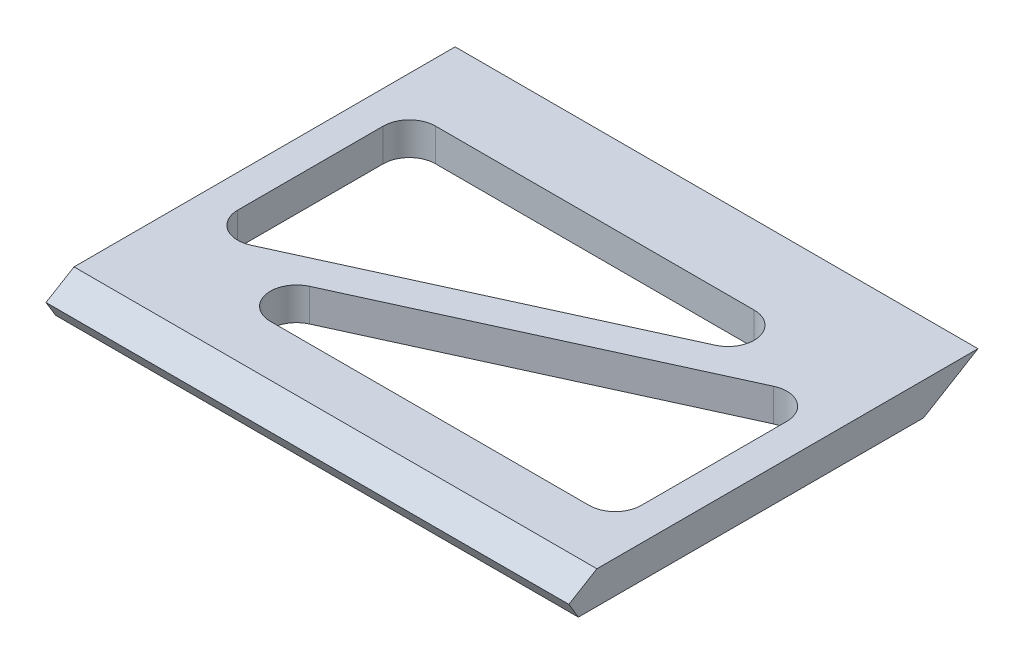
SolidWorks part; units mm, degrees
material "Balsa"
ref_plane "Front Plane" through (0, 0, 0) normal (0, 0, 1) x (1, 0, 0)
ref_plane "Top Plane" through (0, 0, 0) normal (0, 1, 0) x (1, 0, 0)
ref_plane "Right Plane" through (0, 0, 0) normal (1, 0, 0) x (0, 0, -1)
sketch "Sketch3" plane through (71.1933, 0, 0) normal (1, 0, 0) x (0, 0, -1)
  line L0 (56.968, 6.35) -> (46.3846, 0)
  line L1 (46.3846, 0) -> (-20.6804, 0)
  line L2 (-20.6804, 0) -> (-22.5302, 3.083)
  line L3 (-22.5302, 3.083) -> (-108.1269, 145.7441) construction
  line L4 (56.968, 6.35) -> (63.7199, 10.4011) construction
  line L6 (-22.5302, 3.083) -> (-17.0851, 6.35)
  line L7 (-17.0851, 6.35) -> (56.968, 6.35)
extrude "Boss-Extrude2" add sketch "Sketch3" against normal up to surface (101.6 mm away)
sketch "Sketch4" plane through (0, 6.35, 0) normal (0, 1, 0) x (1, 0, 0)
  line L0 (-30.4067, -17.0851) -> (-30.4067, 56.968) construction
  line L1 (-18.9767, 41.728) -> (42.949, 41.728)
  line L2 (-24.0567, 36.648) -> (-24.0567, 8.3732)
  line L3 (-2.1624, -7.1791) -> (59.7633, -7.1791)
  line L4 (64.8433, 26.1757) -> (64.8433, -2.0991)
  line L5 (-30.4067, 56.968) -> (71.1933, 56.968) construction
  line L6 (71.1933, 56.968) -> (71.1933, -17.0851) construction
  line L7 (-30.4067, -17.0851) -> (71.1933, -17.0851) construction
  line L8 (-16.8668, 3.7521) -> (45.0589, 32.0269)
  line L9 (-4.2724, 2.522) -> (57.6533, 30.7968)
  line L10 (-29.6117, -5.5575) -> (68.6464, 39.3064)
  arc A0 (-4.2724, 2.522) -> (-2.1624, -7.1791) centre (-2.1624, -2.0991) ccw
  arc A1 (59.7633, -7.1791) -> (64.8433, -2.0991) centre (59.7633, -2.0991) ccw
  arc A2 (57.6533, 30.7968) -> (64.8433, 26.1757) centre (59.7633, 26.1757) cw
  arc A3 (45.0589, 32.0269) -> (42.949, 41.728) centre (42.949, 36.648) ccw
  arc A4 (-18.9767, 41.728) -> (-24.0567, 36.648) centre (-18.9767, 36.648) ccw
  arc A5 (-16.8668, 3.7521) -> (-24.0567, 8.3732) centre (-18.9767, 8.3732) cw
  dimension "D7" = 5.08
  dimension "D1" = 6.35
  dimension "D2" = 15.24
  dimension "D3" = 6.35
  dimension "D4" = 9.906
  dimension "D5" = 3.175
  dimension "D6" = 3.175
extrude "Cut-Extrude1" cut sketch "Sketch4" against normal up to surface (6.35 mm away) contours A5 L8 A3 L1 A4 L2 | A2 L9 A0 L3 A1 L4 region at (4.1335, 6.35, -27.6167) region at (36.6531, 6.35, -6.9321) up to face at (20.3933, 0, -12.8521)
